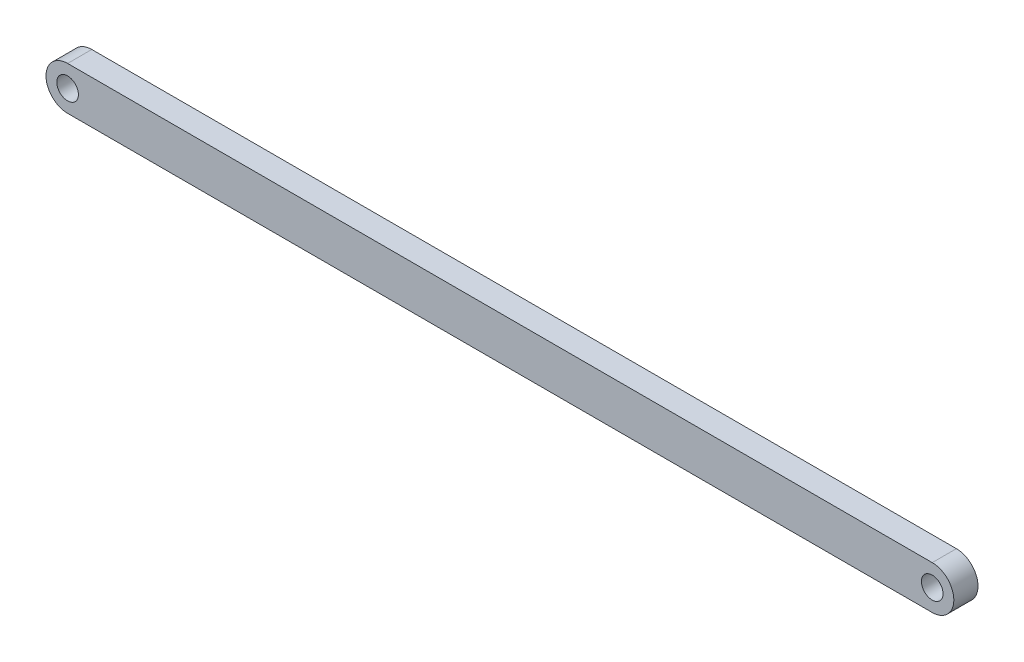
SolidWorks part; units mm, degrees
ref_plane "Front Plane" through (0, 0, 0) normal (0, 0, 1) x (1, 0, 0)
ref_plane "Top Plane" through (0, 0, 0) normal (0, 1, 0) x (1, 0, 0)
ref_plane "Right Plane" through (0, 0, 0) normal (1, 0, 0) x (0, 0, -1)
sketch "Sketch1" plane through (0, 0, 0) normal (0, 0, 1) x (1, 0, 0)
  line L0 (-50.8, 0) -> (50.8, 0) construction
  line L1 (-50.8, 2.54) -> (50.8, 2.54)
  line L2 (-50.8, -2.54) -> (50.8, -2.54)
  arc A0 (-50.8, 2.54) -> (-50.8, -2.54) centre (-50.8, 0) ccw
  arc A1 (50.8, -2.54) -> (50.8, 2.54) centre (50.8, 0) ccw
  circle A2 centre (-50.8, 0) radius 1.27
  circle A3 centre (50.8, 0) radius 1.27
  point P2 (0, 0)
  dimension "D2" = 2.54
  dimension "D3" = 2.54
  dimension "D1" = 101.6
extrude "Boss-Extrude1" add sketch "Sketch1" along normal blind 1.42 and the other way blind 1.42
